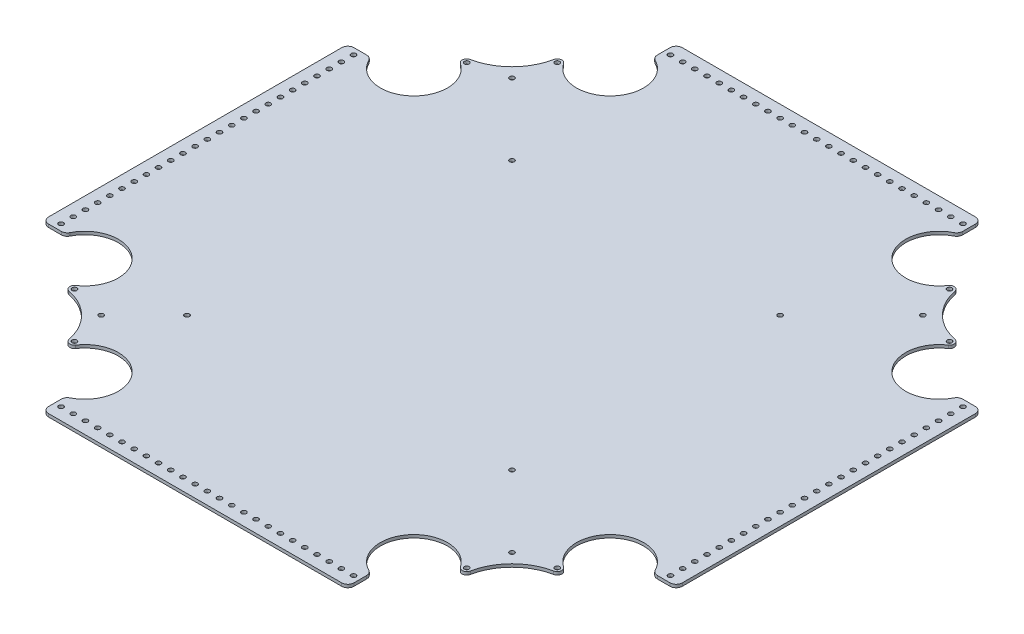
SolidWorks part; units mm, degrees
material "PC High Viscosity"
ref_plane "Front Plane" through (0, 0, 0) normal (0, 0, 1) x (1, 0, 0)
ref_plane "Top Plane" through (0, 0, 0) normal (0, 1, 0) x (1, 0, 0)
ref_plane "Right Plane" through (0, 0, 0) normal (1, 0, 0) x (0, 0, -1)
sketch "Sketch1" plane through (0, 0, 0) normal (0, 1, 0) x (1, 0, 0)
  line L1 (330.2, 330.2) -> (-330.2, 330.2)
  line L2 (330.2, 330.2) -> (330.2, -330.2)
  line L3 (330.2, -330.2) -> (-330.2, -330.2)
  line L4 (-330.2, 330.2) -> (-330.2, -330.2)
  line L5 (330.2, 330.2) -> (-330.2, -330.2) construction
  line L6 (330.2, -330.2) -> (-330.2, 330.2) construction
  point P0 (0, 0)
  dimension "D1" = 660.4
extrude "Boss-Extrude1" add sketch "Sketch1" along normal mid plane 3.175
sketch "Sketch2" plane through (0, 1.5875, 0) normal (0, 1, 0) x (1, 0, 0)
  line L0 (-330.2, -330.2) -> (330.2, -330.2) construction
  line L1 (-330.2, 330.2) -> (-330.2, -330.2) construction
  circle A0 centre (-317.5, -317.5) radius 2.4892
  dimension "D1" = 4.9784
  dimension "D2" = 12.7
  dimension "D3" = 12.7
extrude "Cut-Extrude1" cut sketch "Sketch2" against normal through all
pattern_linear "LPattern1" count 51 spacing 12.7 along (0, 0, -1) count 51 spacing 12.7 along (1, 0, 0) of "Cut-Extrude1" pattern seed only yes
pattern_linear "LPattern2" count 51 spacing 12.7 along (0, 0, -1) of face at (317.5, -1.5875, 319.9892)
pattern_linear "LPattern3" count 50 spacing 12.7 along (1, 0, 0) of face at (-317.5, -1.5875, -315.0108)
sketch "Sketch4" plane through (0, -1.5875, 0) normal (0, -1, 0) x (-1, 0, 0)
  line L0 (-330.2, 159.131) -> (-306.3652, 159.131)
  line L1 (-330.2, -330.2) -> (-330.2, 330.2) construction
  line L2 (-320.675, 160.7185) -> (-314.325, 160.7185) construction
  line L3 (-159.131, 330.2) -> (-159.131, 306.3652)
  line L4 (-330.2, 330.2) -> (330.2, 330.2) construction
  line L5 (-159.131, 330.2) -> (-330.2, 330.2)
  line L6 (-330.2, 330.2) -> (-330.2, 159.131)
  circle A0 centre (-263.525, 263.525) radius 55.5625
  arc A1 (-232.9401, 309.912) -> (-319.0875, 263.525) centre (-263.525, 263.525) ccw construction
  circle A2 centre (-171.45, 273.685) radius 34.925
  circle A3 centre (-273.685, 171.45) radius 34.925
  arc A4 (-140.716, 273.685) -> (-171.45, 304.419) centre (-171.45, 273.685) ccw construction
  arc A5 (-304.8, 171.45) -> (-251.6834, 149.4484) centre (-273.685, 171.45) ccw construction
  arc A6 (-254.2153, 200.4446) -> (-252.5049, 209.0663) centre (-251.5604, 204.3984) cw
  arc A7 (-209.0663, 252.5049) -> (-200.4446, 254.2153) centre (-204.3984, 251.5604) cw
  dimension "D1" = 69.85
  dimension "D2" = 1.5875
  dimension "D3" = 4.7625
extrude "Cut-Extrude2" cut sketch "Sketch4" against normal through all contours A0 A7 A2 L3 L5 L6 L0 A3 A6 | A0 | A3 | A2 region at (327.7807, -1.5875, -244.6655) region at (273.685, -1.5875, -171.45) region at (263.525, -1.5875, -263.525) region at (171.45, -1.5875, -273.685)
mirror "Mirror2" about plane through (0, 0, 0) normal (1, 0, 0) of "Cut-Extrude2"
mirror "Mirror3" about plane through (0, 0, 0) normal (0, 0, 1) of "Cut-Extrude2", "Mirror2"
fillet "Fillet1" radius 6.35 16 edges at (-330.2, 0, -159.131) (-306.3652, 0, -159.131) (-159.131, 0, -306.3652) (-159.131, 0, -330.2) (159.131, 0, -330.2) (159.131, 0, -306.3652) (306.3652, 0, -159.131) (330.2, 0, -159.131) (330.2, 0, 159.131) (306.3652, 0, 159.131) (159.131, 0, 306.3652) (159.131, 0, 330.2) (-159.131, 0, 330.2) (-159.131, 0, 306.3652) (-330.2, 0, 159.131) (-306.3652, 0, 159.131)
sketch "Sketch5" plane through (0, -1.5875, 0) normal (0, -1, 0) x (1, 0, 0)
  circle A4 centre (139.7, 139.7) radius 2.4892
  circle A5 centre (139.7, -139.7) radius 2.4892
  circle A6 centre (-139.7, -139.7) radius 2.4892
  circle A8 centre (-169.3333, 169.3333) radius 2.4892
  circle A9 centre (-169.3333, 169.3333) radius 2.4892 construction
  circle A10 centre (-139.7, -139.7) radius 2.4892 construction
  circle A11 centre (139.7, -139.7) radius 2.4892 construction
  circle A12 centre (139.7, 139.7) radius 2.4892 construction
  point P1 (0, 0)
  point P3 (0, 0)
  point P7 (0, 0)
  dimension "D1" = 4.9784
extrude "Cut-Extrude3" cut sketch "Sketch5" against normal through all
sketch "Sketch6" plane through (0, 1.5875, 0) normal (0, 1, 0) x (1, 0, 0)
  line L0 (0, 0) -> (0, 23.3452) construction
  line L1 (0, 0) -> (30.1444, 0) construction
  circle A0 centre (-251.5604, -204.3984) radius 2.4892
  circle A1 centre (-204.3984, -251.5604) radius 2.4892
  circle A2 centre (-169.3333, -169.3333) radius 2.4892 construction
  circle A4 centre (-214.0672, -214.0672) radius 2.4892
  arc A5 (-251.5604, -204.3984) -> (-204.3984, -251.5604) centre (-241.0079, -241.0079) cw construction
  arc A6 (251.5604, -204.3984) -> (204.3984, -251.5604) centre (241.0079, -241.0079) ccw construction
  circle A7 centre (214.0672, -214.0672) radius 2.4892
  circle A8 centre (204.3984, -251.5604) radius 2.4892
  circle A9 centre (251.5604, -204.3984) radius 2.4892
  arc A10 (251.5604, 204.3984) -> (204.3984, 251.5604) centre (241.0079, 241.0079) cw construction
  arc A11 (-251.5604, 204.3984) -> (-204.3984, 251.5604) centre (-241.0079, 241.0079) ccw construction
  circle A12 centre (251.5604, 204.3984) radius 2.4892
  circle A13 centre (204.3984, 251.5604) radius 2.4892
  circle A14 centre (214.0672, 214.0672) radius 2.4892
  circle A15 centre (-214.0672, 214.0672) radius 2.4892
  circle A16 centre (-204.3984, 251.5604) radius 2.4892
  circle A17 centre (-251.5604, 204.3984) radius 2.4892
  dimension "D1" = 38.1
extrude "Cut-Extrude4" cut sketch "Sketch6" against normal through all both
